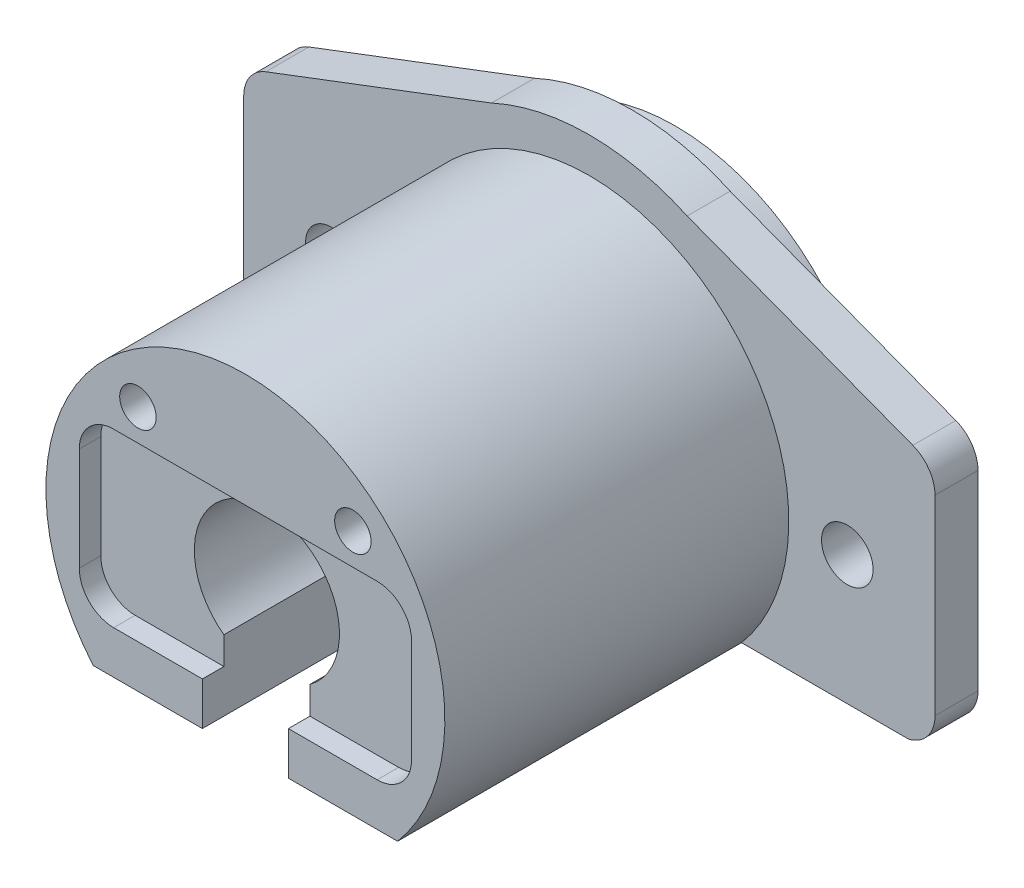
SolidWorks part; units mm, degrees
ref_plane "Front Plane" through (0, 0, 0) normal (0, 0, 1) x (1, 0, 0)
ref_plane "Top Plane" through (0, 0, 0) normal (0, 1, 0) x (1, 0, 0)
ref_plane "Right Plane" through (0, 0, 0) normal (1, 0, 0) x (0, 0, -1)
sketch "Sketch1" plane through (0, 0, 0) normal (0, 0, 1) x (1, 0, 0)
  line L0 (-22.983, 17.4625) -> (21.2496, 17.4625) construction
  line L5 (-7.2748, 15.875) -> (7.2748, 15.875) construction
  line L6 (-25.654, 8.89) -> (-7.2748, 15.875) construction
  line L10 (25.654, -8.89) -> (25.654, 8.89) construction
  line L14 (-25.654, -8.89) -> (-25.654, 8.89) construction
  line L15 (25.654, -8.89) -> (-25.654, 8.89) construction
  line L16 (25.654, 8.89) -> (-25.654, -8.89) construction
  line L17 (7.2748, 15.875) -> (25.654, 8.89) construction
  line L18 (-12.4425, 0) -> (10.4267, 0) construction
  line L19 (7.2748, -15.875) -> (25.654, -8.89) construction
  line L20 (-25.654, -8.89) -> (-7.2748, -15.875) construction
  line L21 (-25.654, 8.89) -> (25.654, 8.89) construction
  line L22 (7.2258, -15.7578) -> (25.527, -8.8024)
  line L23 (25.527, -8.8024) -> (25.527, 8.8024)
  line L24 (7.2258, 15.7578) -> (25.527, 8.8024)
  line L25 (-25.527, 8.8024) -> (-7.2258, 15.7578)
  line L26 (-25.527, -8.8024) -> (-25.527, 8.8024)
  line L27 (-25.527, -8.8024) -> (-7.2258, -15.7578)
  arc A5 (7.2748, 15.875) -> (-7.2748, 15.875) centre (0, 0) ccw construction
  arc A6 (7.2748, -15.875) -> (-7.2748, -15.875) centre (0, 0) cw construction
  circle A7 centre (0, 0) radius 17.4625 construction
  arc A8 (7.2258, 15.7578) -> (-7.2258, 15.7578) centre (0, 0) ccw
  arc A9 (7.2258, -15.7578) -> (-7.2258, -15.7578) centre (0, 0) cw
  dimension "D2" = 1.5875
  dimension "D4" = 51.308
  dimension "D5" = 34.925
  dimension "D1" = 34.925
  dimension "D3" = 17.78
  dimension "D6" = 0.127
extrude "Boss-Extrude1" add sketch "Sketch1" along normal blind 3.175
fillet "Fillet2" radius 2.54 4 edges at (25.527, -8.8024, 1.5875) (25.527, 8.8024, 1.5875) (-25.527, 8.8024, 1.5875) (-25.527, -8.8024, 1.5875)
sketch "Sketch2" plane through (0, 0, 3.175) normal (0, 0, 1) x (1, 0, 0)
  line L0 (19.05, 0) -> (-19.05, 0) construction
  circle A0 centre (19.05, 0) radius 1.905
  circle A1 centre (-19.05, 0) radius 1.905
  dimension "D2" = 3.81
  dimension "D3" = 3.81
  dimension "D1" = 38.1
extrude "Cut-Extrude1" cut sketch "Sketch2" against normal up to vertex (3.175 mm away) up to point (23.8894, -9.4248, 0)
sketch "Sketch3" plane through (0, 0, 3.175) normal (0, 0, 1) x (1, 0, 0)
  circle A0 centre (0, 0) radius 14.732
  dimension "D1" = 29.464
extrude "Boss-Extrude2" add sketch "Sketch3" along normal blind 25.4 and the other way blind 6.35
sketch "Sketch4" plane through (0, 0, 28.575) normal (0, 0, 1) x (1, 0, 0)
  circle A0 centre (0, 0) radius 5.3594
  dimension "D1" = 10.7188
extrude "Cut-Extrude2" cut sketch "Sketch4" against normal through all
sketch "Sketch5" plane through (0, 0, 0) normal (0, 1, 0) x (1, 0, 0)
  line L0 (0, -13.3771) -> (0, 0) construction
  line L1 (3.175, -32.9113) -> (-3.175, -32.9113)
  line L2 (3.175, -32.9113) -> (3.175, 6.157)
  line L3 (3.175, 6.157) -> (-3.175, 6.157)
  line L4 (-3.175, -32.9113) -> (-3.175, 6.157)
  line L5 (3.175, -32.9113) -> (-3.175, 6.157) construction
  line L6 (3.175, 6.157) -> (-3.175, -32.9113) construction
  point P0 (0, -13.3771)
  dimension "D1" = 6.35
extrude "Cut-Extrude3" cut sketch "Sketch5" against normal through all
ref_plane "Plane1" through (0, -12.7, 0) normal (0, 1, 0) x (1, 0, 0)
sketch "Sketch6" plane through (0, -12.7, 0) normal (0, 1, 0) x (1, 0, 0)
  line L5 (0, 8.9082) -> (0, -18.165) construction
  line L7 (26.8882, -32.3375) -> (-26.8882, -32.3375)
  line L8 (26.8882, -32.3375) -> (26.8882, 9.8167)
  line L9 (26.8882, 9.8167) -> (-26.8882, 9.8167)
  line L10 (-26.8882, -32.3375) -> (-26.8882, 9.8167)
  line L11 (26.8882, -32.3375) -> (-26.8882, 9.8167) construction
  line L12 (26.8882, 9.8167) -> (-26.8882, -32.3375) construction
  point P2 (0, -11.2604)
extrude "Cut-Extrude4" cut sketch "Sketch6" against normal through all and the other way blind 3.175
sketch "Sketch8" plane through (0, 0, 28.575) normal (0, 0, 1) x (1, 0, 0)
  line L1 (-12.2682, 6.35) -> (12.2682, 6.35)
  line L2 (-12.2682, 6.35) -> (-12.2682, -6.35)
  line L3 (-12.2682, -6.35) -> (12.2682, -6.35)
  line L4 (12.2682, 6.35) -> (12.2682, -6.35)
  line L5 (-12.2682, 6.35) -> (12.2682, -6.35) construction
  line L6 (-12.2682, -6.35) -> (12.2682, 6.35) construction
  point P0 (0, 0)
  dimension "D1" = 24.5364
  dimension "D2" = 12.7
extrude "Cut-Extrude5" cut sketch "Sketch8" against normal blind 1.5875
fillet "Fillet4" radius 2.54 4 edges at (12.2682, 6.35, 27.7812) (12.2682, -6.35, 27.7812) (-12.2682, 6.35, 27.7812) (-12.2682, -6.35, 27.7812)
sketch "Sketch9" plane through (0, 0, 26.9875) normal (0, 0, 1) x (1, 0, 0)
  line L0 (7.9375, 8.6623) -> (-7.9375, 8.6623) construction
  line L1 (0, 0) -> (0, 8.6623) construction
  circle A0 centre (7.9375, 8.6623) radius 1.3462
  circle A1 centre (-7.9375, 8.6623) radius 1.3462
  dimension "D1" = 2.6924
  dimension "D2" = 15.875
extrude "Cut-Extrude6" cut sketch "Sketch9" against normal blind 9.525 and the other way up to vertex (1.5875 mm away) other way up to point (11.2386, -9.525, 28.575)
sketch "Sketch10" plane through (0, -9.525, 0) normal (0, -1, 0) x (1, 0, 0)
  line L0 (0, 0) -> (0, 26.9875) construction
  line L1 (9.7282, 26.9875) -> (-9.7282, 26.9875) construction
  line L2 (-11.2386, 11.7475) -> (23.3411, 11.7475) construction
  line L3 (-11.2386, 11.938) -> (11.2386, 11.938)
  line L4 (-11.2386, 11.938) -> (-11.2386, 11.557)
  line L5 (-11.2386, 11.557) -> (11.2386, 11.557)
  line L6 (11.2386, 11.938) -> (11.2386, 11.557)
  line L7 (-11.2386, 11.938) -> (11.2386, 11.557) construction
  line L8 (-11.2386, 11.557) -> (11.2386, 11.938) construction
  line L9 (-5.0216, 14.0079) -> (-10.0545, 14.0079) construction
  line L10 (-4.5661, 5.3651) -> (-10.57, 5.3651) construction
  line L11 (11.2386, 26.9875) -> (-11.2386, 26.9875) construction
  line L12 (11.2386, 3.175) -> (11.2386, 28.575) construction
  line L13 (-11.2386, 28.575) -> (-11.2386, 3.175) construction
  line L14 (11.2386, 28.575) -> (3.175, 28.575) construction
  line L15 (11.2386, 7.4975) -> (-11.2386, 7.4975) construction
  line L16 (-11.2386, 3.438) -> (11.2386, 3.057) construction
  line L17 (-11.2386, 3.057) -> (11.2386, 3.438) construction
  line L18 (-11.2386, 3.2475) -> (23.3411, 3.2475) construction
  line L19 (11.2386, 3.057) -> (11.2386, 3.438)
  line L20 (-11.2386, 3.438) -> (11.2386, 3.438)
  line L21 (-11.2386, 3.057) -> (-11.2386, 3.438)
  line L22 (-11.2386, 3.057) -> (11.2386, 3.057)
  text T0 "3mL" font "Century Gothic" height 1.5875
  text T1 "2.5mL" font "Century Gothic" height 1.5875
  point P5 (0, 11.7475)
  point P28 (0, 3.2475)
  dimension "D1" = 0.381
  dimension "D2" = 1.5875
  dimension "D3" = 15.24
  dimension "D4" = 4.25
extrude "Cut-Extrude7" cut sketch "Sketch10" against normal blind 0.7937
